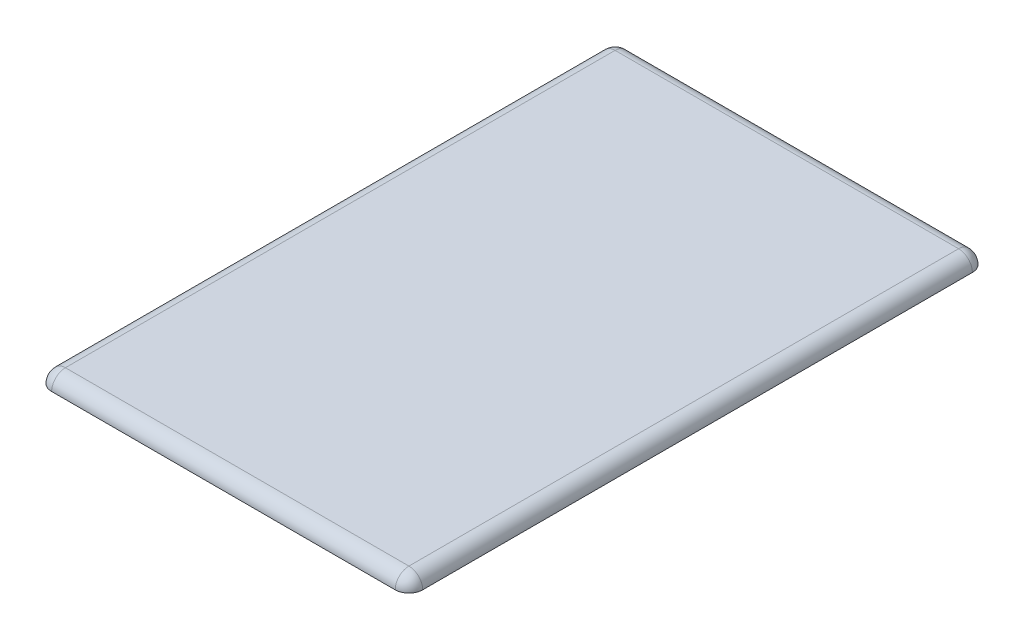
SolidWorks part; units mm, degrees
ref_plane "正面" through (0, 0, 0) normal (0, 0, 1) x (1, 0, 0)
ref_plane "平面" through (0, 0, 0) normal (0, 1, 0) x (1, 0, 0)
ref_plane "右側面" through (0, 0, 0) normal (1, 0, 0) x (0, 0, -1)
sketch "ｽｹｯﾁ1" plane through (0, 0, 0) normal (0, 1, 0) x (1, 0, 0)
  line L0 (-7.0843, 28.95) -> (17.7157, 28.95)
  line L1 (-7.0843, 28.95) -> (-7.0843, -10.85)
  line L2 (17.7157, 28.95) -> (17.7157, -10.85)
  line L3 (-7.0843, -10.85) -> (17.7157, -10.85)
  dimension "D1" = 24.8
  dimension "D2" = 39.8
extrude "ﾎﾞｽ - 押し出し1" add sketch "ｽｹｯﾁ1" along normal blind 0.8
sketch "ｽｹｯﾁ2" plane through (0, 0.8, 0) normal (0, 1, 0) x (1, 0, 0)
  line L2 (-8.1843, 30.05) -> (18.8157, 30.05)
  line L3 (-8.1843, 30.05) -> (-8.1843, -11.95)
  line L4 (18.8157, 30.05) -> (18.8157, -11.95)
  line L5 (-8.1843, -11.95) -> (18.8157, -11.95)
  line L8 (-7.0843, 28.95) -> (-7.0843, -10.85) construction
  point P0 (-7.0843, 9.05)
  point P5 (5.3157, 9.05)
  point P8 (5.3157, 9.05)
  dimension "D1" = 12.4
  dimension "D2" = 13.5
  dimension "D3" = 27
  dimension "D4" = 42
  dimension "D5" = 21
extrude "ﾎﾞｽ - 押し出し2" add sketch "ｽｹｯﾁ2" along normal blind 1
fillet "ﾌｨﾚｯﾄ1" radius 1 4 edges at (-8.1843, 1.8, -9.05) (5.3157, 1.8, -30.05) (18.8157, 1.8, -9.05) (5.3157, 1.8, 11.95)
